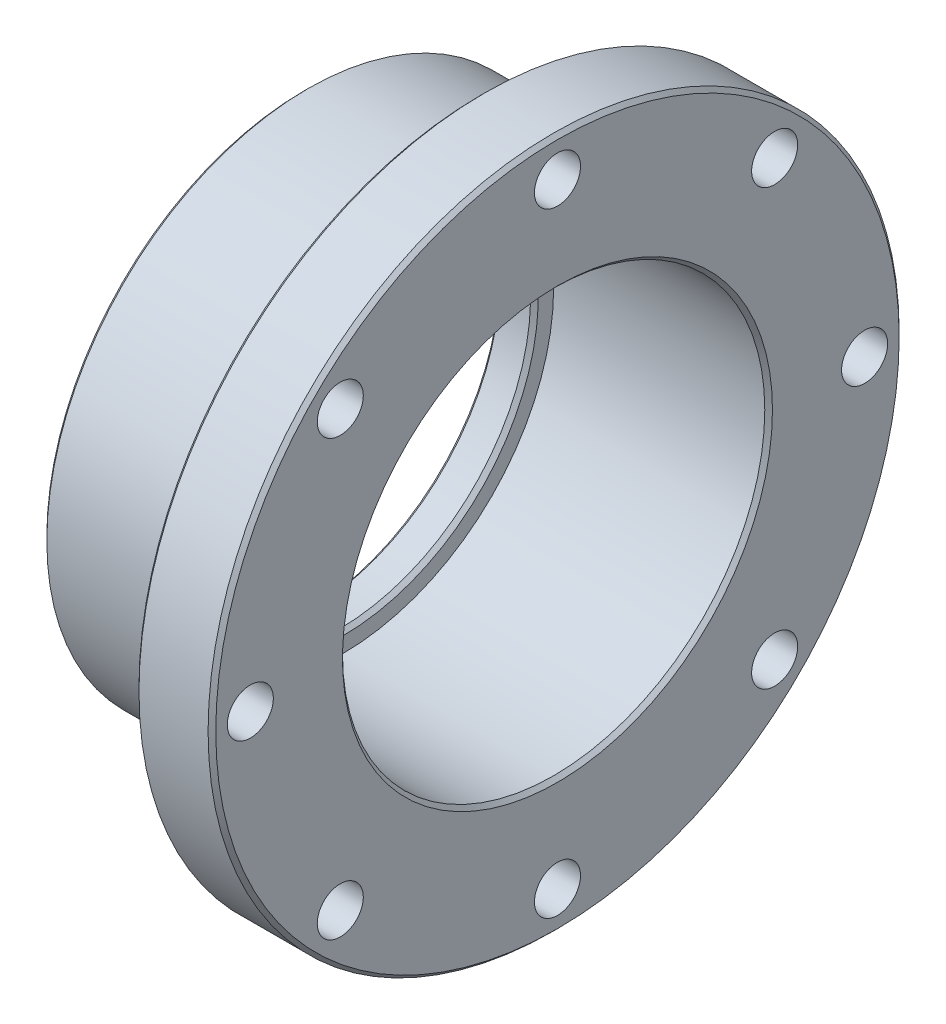
SolidWorks part; units mm, degrees
ref_plane "前视基准面" through (0, 0, 0) normal (0, 0, 1) x (1, 0, 0)
ref_plane "上视基准面" through (0, 0, 0) normal (0, 1, 0) x (1, 0, 0)
ref_plane "右视基准面" through (0, 0, 0) normal (1, 0, 0) x (0, 0, -1)
other "Configuration Table"
sketch "草图1" plane through (0, 0, 0) normal (0, 0, 1) x (1, 0, 0)
  line L0 (0, 0) -> (0, 34)
  line L1 (0, 34) -> (23, 34)
  line L2 (23, 34) -> (23, 45)
  line L3 (23, 45) -> (33, 45)
  line L4 (33, 45) -> (33, 0)
  line L5 (33, 0) -> (0, 0)
  line L6 (0, 0) -> (-22.3549, 0) construction
  dimension "D1" = 68
  dimension "D2" = 90
  dimension "D3" = 23
  dimension "D4" = 33
revolve "旋转1" add sketch "草图1" angle 360 about L6
sketch "草图2" plane through (0, 0, 0) normal (0, 0, 1) x (1, 0, 0)
  line L0 (0, 0) -> (-12.3125, 0) construction
  line L1 (0, 34) -> (0, -34) construction
  line L2 (0, 0) -> (0, 25)
  line L3 (0, 25) -> (5, 25)
  line L4 (5, 25) -> (5, 27.5)
  line L5 (5, 27.5) -> (33, 27.5)
  line L6 (33, -45) -> (33, 45) construction
  line L7 (33, 27.5) -> (33, 0)
  line L8 (33, 0) -> (0, 0)
  dimension "D1" = 50
  dimension "D2" = 55
  dimension "D3" = 28
revolve "切除-旋转1" cut sketch "草图2" angle 360 about L0
sketch "草图3" plane through (23, 0, 0) normal (-1, 0, 0) x (0, 0, 1)
  circle A0 centre (0, 40) radius 3
  circle A1 centre (28.2843, 28.2843) radius 3
  circle A2 centre (40, 0) radius 3
  circle A3 centre (28.2843, -28.2843) radius 3
  circle A4 centre (0, -40) radius 3
  circle A5 centre (-28.2843, -28.2843) radius 3
  circle A6 centre (-40, 0) radius 3
  circle A7 centre (-28.2843, 28.2843) radius 3
  point P2 (0, 0)
  point P4 (42.1996, 2.1432)
  point P5 (0, 0)
  point P20 (0, 0)
  dimension "D1" = 40
  dimension "D2" = 6
  dimension "D3" = 8
extrude "切除-拉伸1" cut sketch "草图3" against normal up to next
chamfer "倒角1" distance 0.5 angle 45 6 edges at (5, 25, 0) (33, 27.5, 0) (33, 0, -45) (23, 0, -45) (0, 0, -34) (0, 25, 0)
